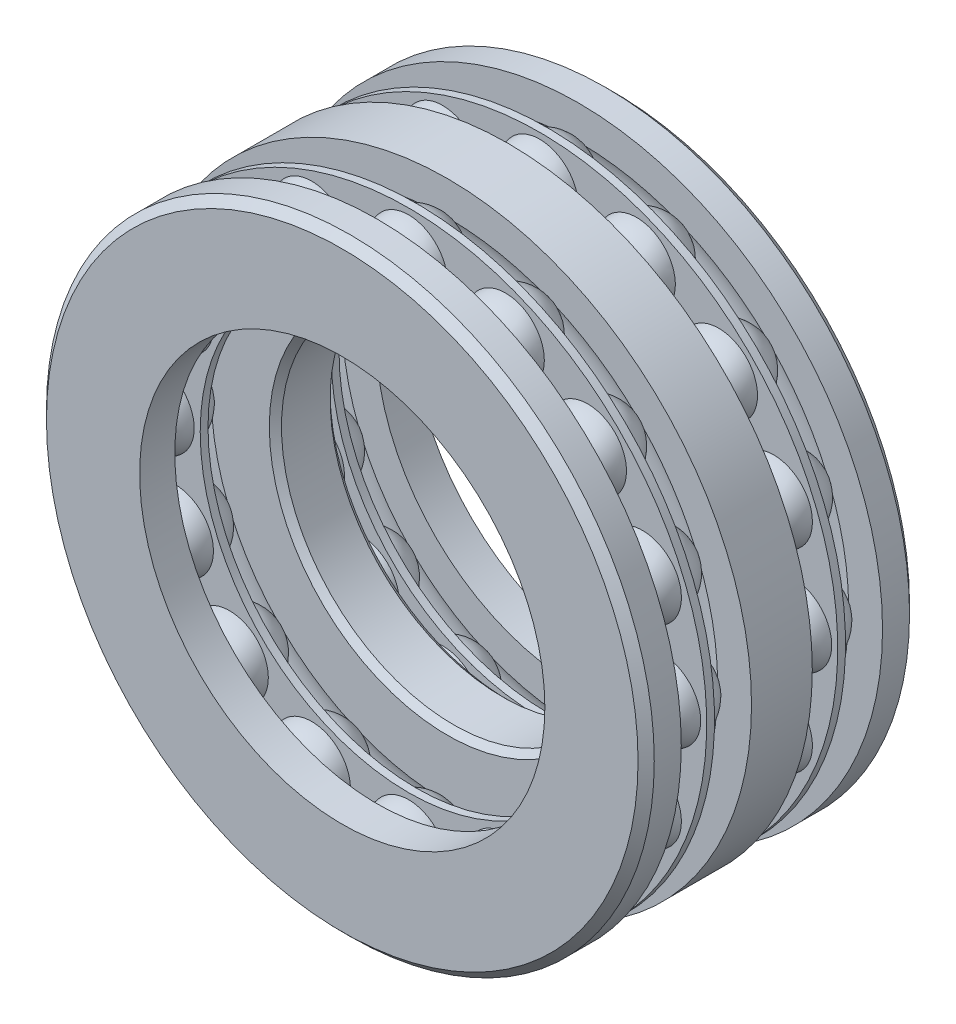
SolidWorks part; units mm, degrees
ref_plane "Front Plane" through (0, 0, 0) normal (0, 0, 1) x (1, 0, 0)
ref_plane "Top Plane" through (0, 0, 0) normal (0, 1, 0) x (1, 0, 0)
ref_plane "Right Plane" through (0, 0, 0) normal (1, 0, 0) x (0, 0, -1)
sketch "BaseSke" plane through (0, 0, 0) normal (1, 0, 0) x (0, 0, -1)
  line L0 (-28.5883, 0) -> (28.5883, 0) construction
  line L1 (0, 0) -> (0, 88.5589) construction
  line L2 (-7.5, 75) -> (-7.5, 42.5) construction
  line L3 (-33.5, 75) -> (-33.5, 50) construction
  line L4 (-16.1667, 72.1296) -> (-16.1667, 52.8704)
  arc A0 (-16.1667, 52.8704) -> (-16.1667, 72.1296) centre (-16.1667, 62.5) ccw
  dimension "D2" = 19.2593
  dimension "D1" = 125
  dimension "D3" = 8.6667
revolve "Ball" add sketch "BaseSke" angle 360 about L4
sketch "InnerRaceSke" plane through (0, 0, 0) normal (1, 0, 0) x (0, 0, -1)
  line L0 (0, 0) -> (0, 88.5589) construction
  line L1 (0, 75) -> (-7.5, 75)
  line L2 (0, 75) -> (0, 42.5)
  line L3 (0, 42.5) -> (-7.5, 42.5)
  line L4 (-7.5, 75) -> (-7.5, 66.6514)
  line L5 (-7.5, 58.3486) -> (-7.5, 42.5)
  line L6 (-29.2668, 0) -> (26.4528, 0) construction
  arc A0 (-7.5, 58.3486) -> (-7.5, 66.6514) centre (-16.1667, 62.5) ccw
  arc A1 (-16.1667, 52.8704) -> (-16.1667, 72.1296) centre (-16.1667, 62.5) ccw construction
  dimension "D1" = 0.02
revolve "InnerRace" add sketch "InnerRaceSke" angle 360 about L6
sketch "OuterRaceSke" plane through (0, 0, 0) normal (1, 0, 0) x (0, 0, -1)
  line L0 (-24.8333, 58.3486) -> (-24.8333, 50)
  line L1 (-33.5, 75) -> (-24.8333, 75)
  line L2 (-33.5, 75) -> (-33.5, 50)
  line L3 (-33.5, 50) -> (-24.8333, 50)
  line L4 (-24.8333, 75) -> (-24.8333, 66.6514)
  line L5 (-29.2668, 0) -> (29.2668, 0) construction
  arc A0 (-24.8333, 66.6514) -> (-24.8333, 58.3486) centre (-16.1667, 62.5) ccw
  arc A1 (-16.1667, 52.8704) -> (-16.1667, 72.1296) centre (-16.1667, 62.5) ccw construction
  dimension "D1" = 0.02
revolve "OuterRace" add sketch "OuterRaceSke" angle 360 about L5
sketch "CageSke" plane through (0, 0, 0) normal (1, 0, 0) x (0, 0, -1)
  line L0 (-16.1667, 79.3806) -> (-16.1667, 44.5) construction
  line L1 (-17.1296, 73.5741) -> (-15.2037, 73.5741)
  line L2 (-17.1296, 73.5741) -> (-17.1296, 51.4259)
  line L3 (-17.1296, 51.4259) -> (-15.2037, 51.4259)
  line L4 (-15.2037, 73.5741) -> (-15.2037, 51.4259)
  line L5 (-16.1667, 72.1296) -> (-16.1667, 52.8704) construction
  line L6 (-28.0222, 62.5) -> (-4.3111, 62.5) construction
  line L7 (0, 0) -> (-54.0573, 0) construction
  dimension "D1" = 1.9259
  dimension "D2" = 22.1481
revolve "Cage" add sketch "CageSke" angle 360 about L7
chamfer "Chamfer1" distance 2 angle 45 1 edges at (75, 0, 33.5)
chamfer "Chamfer2" distance 1.5 angle 45 1 edges at (42.5, 0, 7.5)
pattern_circular "CirPatternBall" count 16 over 360 about axis through (0, 0, 29.2668) along (0, 0, -1) of "Ball"
sketch "SimplifiedSke" plane through (0, 0, 0) normal (1, 0, 0) x (0, 0, -1)
  line L0 (0, 0) -> (-53.2433, 0) construction
  circle A0 centre (-16.1667, 62.5) radius 9.6296
  arc A1 (-16.1667, 52.8704) -> (-16.1667, 72.1296) centre (-16.1667, 62.5) ccw construction
revolve "Simplified" [suppressed] add sketch "SimplifiedSke" angle 360 about L0
mirror "MirrorBody" about plane through (0, 0, 0) normal (0, 0, 1) of bodies 104
equation "\"D1@BaseSke\" =  ( \"Bearing_Outside_Diameter@BaseSke\" + \"Shoulder_Diameter@BaseSke\" )  / 2"
equation "\"D2@BaseSke\" =  ( \"Bearing_Thickness@BaseSke\" - \"Middle_Thickness@BaseSke\" )  / 2.7"
equation "\"D3@BaseSke\" =  ( \"Bearing_Thickness@BaseSke\" - \"Middle_Thickness@BaseSke\" )  / 6"
equation "\"D1@CageSke\" = \"D2@BaseSke\"/10"
equation "\"D2@CageSke\" = \"D2@BaseSke\" * 1.15"
equation "\"D1@CirPatternBall\" =  int( \"D1@BaseSke\" *  pi  / \"D2@BaseSke\" * 0.8 ) "
